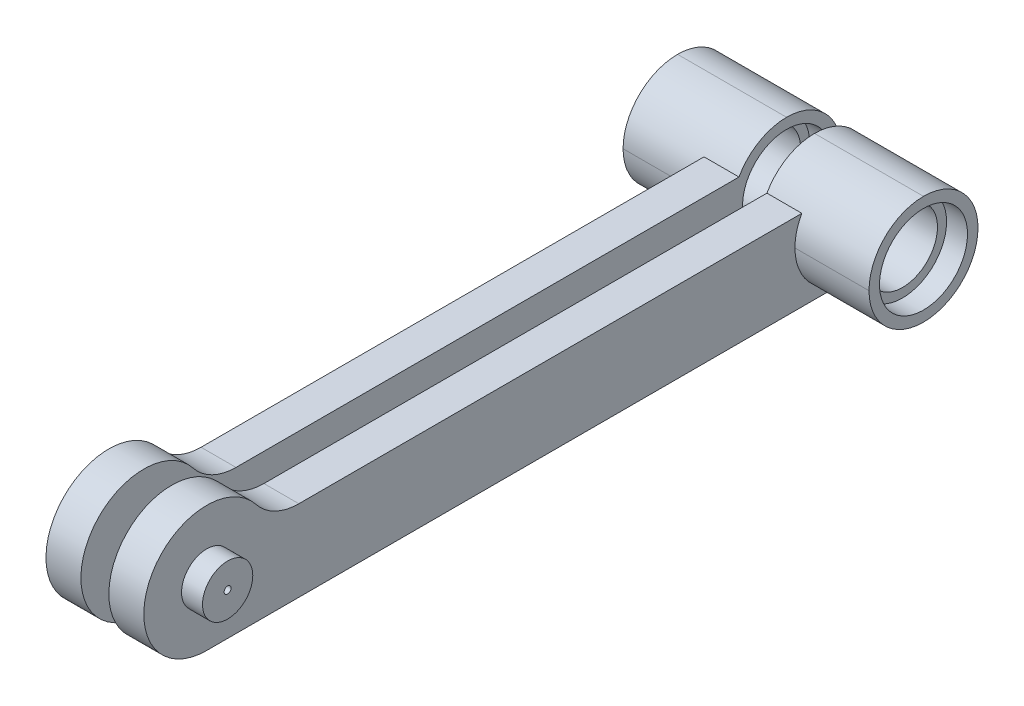
SolidWorks part; units mm, degrees
ref_plane "前视基准面" through (0, 0, 0) normal (0, 0, 1) x (1, 0, 0)
ref_plane "上视基准面" through (0, 0, 0) normal (0, 1, 0) x (1, 0, 0)
ref_plane "右视基准面" through (0, 0, 0) normal (1, 0, 0) x (0, 0, -1)
other "Configuration Table"
sketch "草图1" plane through (0, 0, 0) normal (1, 0, 0) x (0, 0, -1)
  line L0 (46, 3.3) -> (46, -4.5) construction
  line L1 (0, -4.5) -> (49.9, -4.5)
  line L2 (0, -4.5) -> (0, 3.3)
  line L3 (0, 3.3) -> (49.9, 3.3)
  line L4 (49.9, -4.5) -> (49.9, 3.3)
  line L6 (42.1, -4.5) -> (49.9, -4.5)
  line L7 (42.1, -4.5) -> (42.1, 3.3)
  line L8 (42.1, 3.3) -> (49.9, 3.3)
  line L9 (49.9, -4.5) -> (49.9, 3.3)
  line L10 (42.1, -4.5) -> (49.9, 3.3) construction
  line L11 (42.1, 3.3) -> (49.9, -4.5) construction
  circle A4 centre (0, 0) radius 1.8
  circle A5 centre (0, 0) radius 4.5
  circle A6 centre (46, -0.6) radius 2.5
  circle A7 centre (46, -0.6) radius 3.15
  circle A8 centre (0, 0) radius 0.25
  point P9 (46, -0.6)
  dimension "D1" = 3.6
  dimension "D4" = 46
  dimension "D5" = 3.9
  dimension "D2" = 9
  dimension "D6" = 5
  dimension "D7" = 6.3
  dimension "D8" = 0.5
  dimension "D3" = 7.8
extrude "凸台-拉伸1" add sketch "草图1" along normal blind 2.5 contours A5 | L3 L4 L1 L2
extrude "凸台-拉伸3" add sketch "草图1<6>" along normal blind 1.5 from surface contours L2 A4 | L2 A4 region at (0, 0, 0.7769) region at (0, 0, -0.7769) starting at face at (2.5, -0.0392, -24.2851)
sketch "草图1<6>" plane through (0, 0, 0) normal (1, 0, 0) x (0, 0, -1) same geometry as "草图1"
extrude "凸台-拉伸2" add sketch "草图1<5>" along normal blind 7.8 contours A6 | A7 A6 | L7 L1 L4 L3 A7 region at (0, -0.6, -42.2103) region at (0, -0.6, -46) region at (0, -0.6, -42.9391)
sketch "草图1<5>" plane through (0, 0, 0) normal (1, 0, 0) x (0, 0, -1) same geometry as "草图1"
extrude "切除-拉伸1" cut sketch "草图1<7>" along normal through all contours A6 region at (0, -0.6, -46)
sketch "草图1<7>" plane through (0, 0, 0) normal (1, 0, 0) x (0, 0, -1) same geometry as "草图1"
extrude "切除-拉伸2" cut sketch "草图1<8>" along normal blind 1.5 contours A7 A6 region at (0, -0.6, -42.9391)
sketch "草图1<8>" plane through (0, 0, 0) normal (1, 0, 0) x (0, 0, -1) same geometry as "草图1"
extrude "切除-拉伸3" cut sketch "草图1<9>" against normal blind 1.5 from surface contours A7 A6 region at (0, -0.6, -42.9391) starting at face at (7.8, -0.6, -48.5)
sketch "草图1<9>" plane through (0, 0, 0) normal (1, 0, 0) x (0, 0, -1) same geometry as "草图1"
sketch "草图2" plane through (0, 0, 0) normal (-1, 0, 0) x (0, 0, 1)
  line L0 (-3.0594, 3.3) -> (-49.9, 3.3) construction
  line L1 (-42.1, 3.3) -> (-4.5, 3.3)
  line L2 (-42.1, 3.3) -> (-42.1, 1.3)
  line L3 (-42.1, 1.3) -> (-4.5, 1.3)
  line L4 (-4.5, 3.3) -> (-4.5, 1.3)
  line L5 (-42.1, 3.3) -> (-42.1, -4.5) construction
  line L6 (-4.5, 3.3) -> (-3.0594, 3.3)
  line L8 (-4.5, 1.3) -> (-4.3081, 1.3)
  line L9 (-4.5, 1.3) -> (-4.5, 3.3)
  line L10 (-4.5, 3.3) -> (-4.3081, 3.3)
  line L11 (-4.3081, 1.3) -> (-4.3081, 3.3)
  arc A1 (0, -4.5) -> (-3.0594, 3.3) centre (0, 0) ccw construction
  circle A2 centre (0, 0) radius 4.5
  line M7 (-3.0594, 3.3) -> (-49.9, 3.3)
  dimension "D1" = 2
extrude "切除-拉伸4" cut sketch "草图2" against normal through all contours A2 L11 M7 | L8 L11 L6 L4 | L4 L2 L3 M7 region at (0, 2.3, -23.3) region at (0, 2.3, -4.4041) region at (0, 2.7076, -3.9302)
fillet "圆角1" radius 3.9 5 edges at (3.9, -4.5, -49.9) (3.9, 3.3, -49.9) (5.15, -4.5, -42.1) (3.9, 3.3, -42.1) (1.25, 1.3, -4.3081)
ref_plane "基准面1" through (-1, 0, 0) normal (-1, 0, 0) x (0, 0, 1)
mirror "镜向2" about plane through (-1, 0, 0) normal (-1, 0, 0) of bodies 118 114
